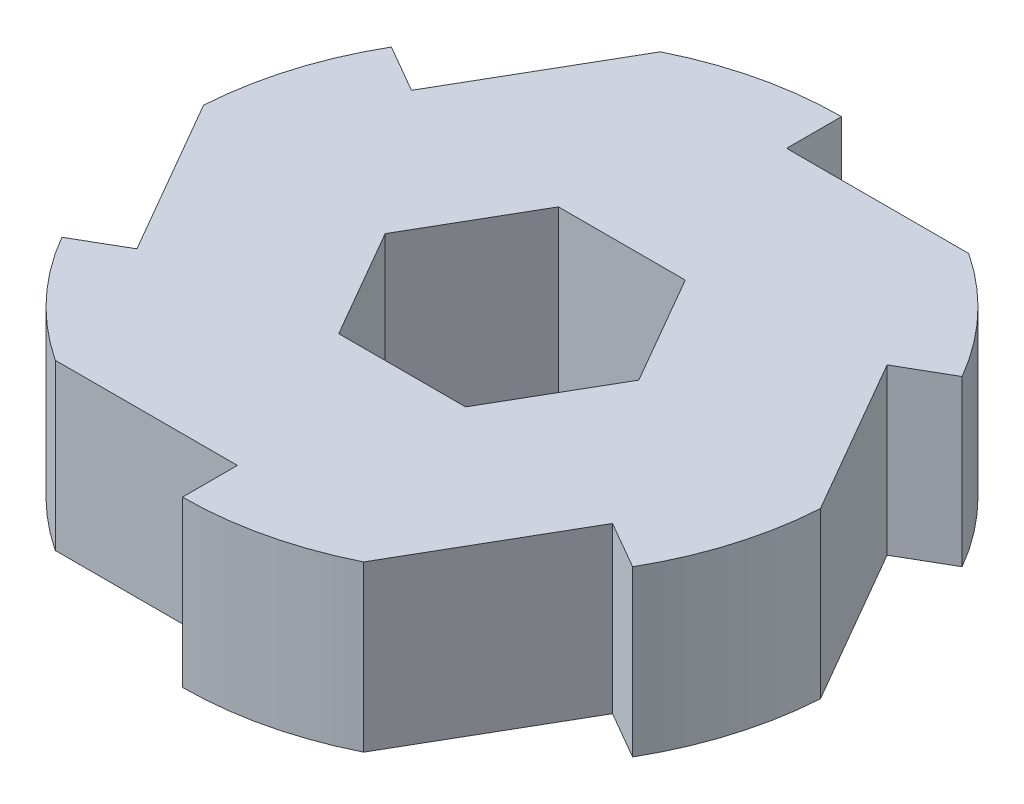
SolidWorks part; units mm, degrees
material "6061-T6 (SS)"
ref_plane "Front" through (0, 0, 0) normal (0, 0, 1) x (1, 0, 0)
ref_plane "Top" through (0, 0, 0) normal (0, 1, 0) x (1, 0, 0)
ref_plane "Right" through (0, 0, 0) normal (1, 0, 0) x (0, 0, -1)
sketch "Sketch2" plane through (0, 0, 0) normal (0, 1, 0) x (1, 0, 0)
  circle A0 centre (0, 0) radius 19.05
  dimension "D1" = 38.1
extrude "Boss-Extrude2" add sketch "Sketch2" along normal blind 9.525
sketch "Sketch3" plane through (0, 9.525, 0) normal (0, 1, 0) x (1, 0, 0)
  line L0 (0, 19.05) -> (0, 15.875)
  line L1 (0, 15.875) -> (10.5303, 15.875)
  circle A0 centre (0, 0) radius 19.05 construction
  point P4 (-2.1198, 16.9338)
  point P6 (10.7065, 15.7567)
  dimension "D1" = 3.175
extrude "Cut-Extrude1" cut sketch "Sketch3" against normal through all and the other way through all
pattern_circular "CirPattern1" count 6 over 360 about axis through (0, 9.525, 0) along (0, -1, 0) of "Cut-Extrude1" reverse direction yes
sketch "Sketch4" plane through (0, 9.525, 0) normal (0, 1, 0) x (1, 0, 0)
  line L1 (7.3323, 0) -> (3.6662, 6.35)
  line L2 (3.6662, 6.35) -> (-3.6662, 6.35)
  line L3 (-3.6662, 6.35) -> (-7.3323, 0)
  line L4 (-7.3323, 0) -> (-3.6662, -6.35)
  line L5 (-3.6662, -6.35) -> (3.6662, -6.35)
  line L6 (3.6662, -6.35) -> (7.3323, 0)
  circle A0 centre (0, 0) radius 6.35 construction
  point P1 (0, 6.35)
  dimension "D1" = 12.7
extrude "Cut-Extrude2" cut sketch "Sketch4" against normal through all
